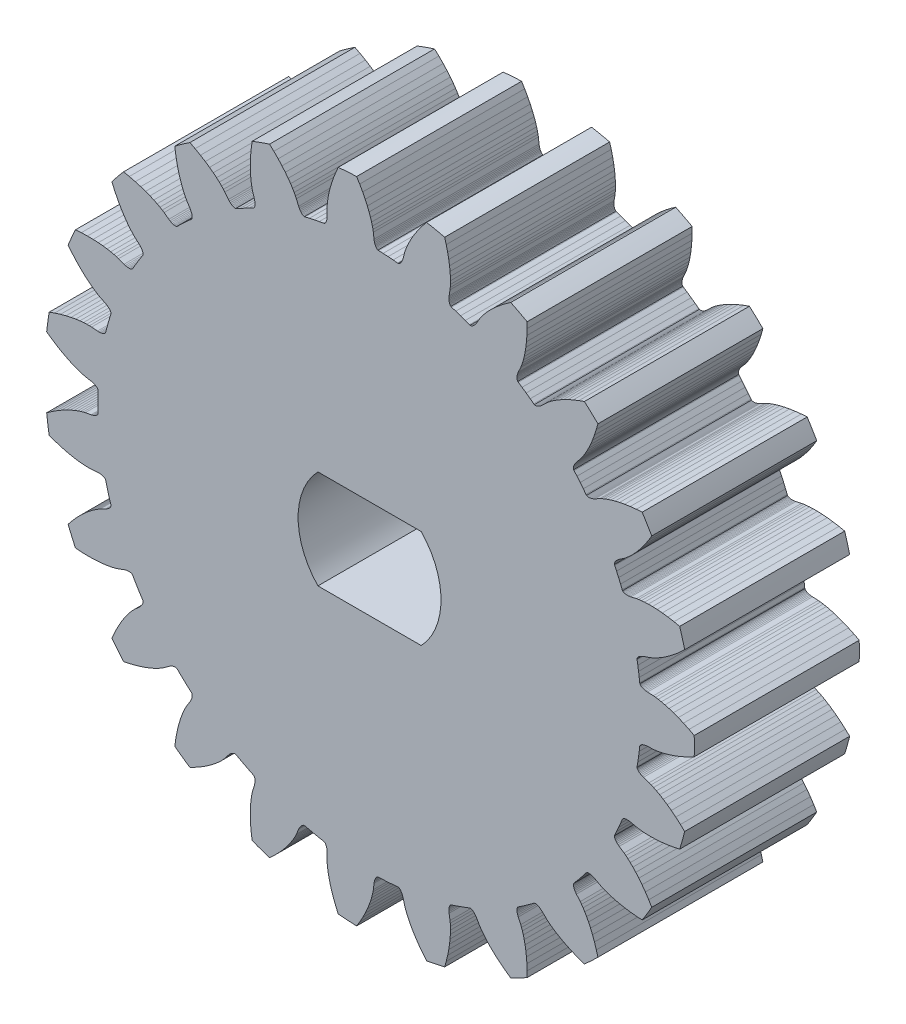
SolidWorks part; units mm, degrees
ref_plane "Front Plane" through (0, 0, 0) normal (0, 0, 1) x (1, 0, 0)
ref_plane "Top Plane" through (0, 0, 0) normal (0, 1, 0) x (1, 0, 0)
ref_plane "Right Plane" through (0, 0, 0) normal (1, 0, 0) x (0, 0, -1)
sketch "Model" plane through (0, 0, 0) normal (0, 0, 1) x (1, 0, 0)
  line L0 (11.9632, 2.8748) -> (11.7845, 2.7201)
  line L1 (11.7845, 2.7201) -> (11.6135, 2.5841)
  line L2 (11.6135, 2.5841) -> (11.4533, 2.4673)
  line L3 (11.4533, 2.4673) -> (11.3032, 2.3672)
  line L4 (11.3032, 2.3672) -> (11.1651, 2.2832)
  line L5 (11.1651, 2.2832) -> (11.0407, 2.2146)
  line L6 (11.0407, 2.2146) -> (10.931, 2.1599)
  line L7 (10.931, 2.1599) -> (10.8362, 2.1174)
  line L8 (10.8362, 2.1174) -> (10.7574, 2.086)
  line L9 (10.7574, 2.086) -> (10.5425, 2.0156)
  line L10 (10.5425, 2.0156) -> (10.4931, 1.9951)
  line L11 (10.4931, 1.9951) -> (10.4491, 1.9736)
  line L12 (10.4491, 1.9736) -> (10.4106, 1.9511)
  line L13 (10.4106, 1.9511) -> (10.3777, 1.9281)
  line L14 (10.3777, 1.9281) -> (10.3503, 1.9046)
  line L15 (10.3503, 1.9046) -> (10.3284, 1.881)
  line L16 (10.3284, 1.881) -> (10.312, 1.8573)
  line L17 (10.312, 1.8573) -> (10.3011, 1.834)
  line L18 (10.3011, 1.834) -> (10.2958, 1.811)
  line L19 (10.2958, 1.811) -> (10.2967, 1.7834)
  line L20 (10.2967, 1.7834) -> (10.3247, 1.6136)
  line L21 (10.3247, 1.6136) -> (10.3527, 1.4229)
  line L22 (10.3527, 1.4229) -> (10.3772, 1.2318)
  line L23 (10.3772, 1.2318) -> (10.396, 1.0608)
  line L24 (10.396, 1.0608) -> (10.4026, 1.0339)
  line L25 (10.4026, 1.0339) -> (10.4139, 1.0133)
  line L26 (10.4139, 1.0133) -> (10.4307, 0.9937)
  line L27 (10.4307, 0.9937) -> (10.4529, 0.9753)
  line L28 (10.4529, 0.9753) -> (10.4803, 0.9585)
  line L29 (10.4803, 0.9585) -> (10.513, 0.9433)
  line L30 (10.513, 0.9433) -> (10.551, 0.93)
  line L31 (10.551, 0.93) -> (10.5941, 0.9188)
  line L32 (10.5941, 0.9188) -> (10.6422, 0.9099)
  line L33 (10.6422, 0.9099) -> (10.6954, 0.9035)
  line L34 (10.6954, 0.9035) -> (10.9213, 0.8937)
  line L35 (10.9213, 0.8937) -> (11.0057, 0.8847)
  line L36 (11.0057, 0.8847) -> (11.1084, 0.8694)
  line L37 (11.1084, 0.8694) -> (11.2288, 0.8463)
  line L38 (11.2288, 0.8463) -> (11.3671, 0.8138)
  line L39 (11.3671, 0.8138) -> (11.5227, 0.7702)
  line L40 (11.5227, 0.7702) -> (11.6942, 0.7143)
  line L41 (11.6942, 0.7143) -> (11.88, 0.645)
  line L42 (11.88, 0.645) -> (12.0814, 0.5602)
  line L43 (12.0814, 0.5602) -> (12.2952, 0.4594)
  line L44 (12.2952, 0.4594) -> (12.4949, 0.3553)
  line L45 (12.4949, -0.3553) -> (12.2952, -0.4594)
  line L46 (12.2952, -0.4594) -> (12.0814, -0.5602)
  line L47 (12.0814, -0.5602) -> (11.88, -0.645)
  line L48 (11.88, -0.645) -> (11.6942, -0.7143)
  line L49 (11.6942, -0.7143) -> (11.5227, -0.7702)
  line L50 (11.5227, -0.7702) -> (11.3671, -0.8138)
  line L51 (11.3671, -0.8138) -> (11.2288, -0.8463)
  line L52 (11.2288, -0.8463) -> (11.1084, -0.8694)
  line L53 (11.1084, -0.8694) -> (11.0057, -0.8847)
  line L54 (11.0057, -0.8847) -> (10.9213, -0.8937)
  line L55 (10.9213, -0.8937) -> (10.6954, -0.9035)
  line L56 (10.6954, -0.9035) -> (10.6422, -0.9099)
  line L57 (10.6422, -0.9099) -> (10.5941, -0.9188)
  line L58 (10.5941, -0.9188) -> (10.551, -0.93)
  line L59 (10.551, -0.93) -> (10.513, -0.9433)
  line L60 (10.513, -0.9433) -> (10.4803, -0.9585)
  line L61 (10.4803, -0.9585) -> (10.4529, -0.9753)
  line L62 (10.4529, -0.9753) -> (10.4307, -0.9937)
  line L63 (10.4307, -0.9937) -> (10.4139, -1.0133)
  line L64 (10.4139, -1.0133) -> (10.4026, -1.0339)
  line L65 (10.4026, -1.0339) -> (10.396, -1.0608)
  line L66 (10.396, -1.0608) -> (10.3772, -1.2318)
  line L67 (10.3772, -1.2318) -> (10.3527, -1.4229)
  line L68 (10.3527, -1.4229) -> (10.3247, -1.6136)
  line L69 (10.3247, -1.6136) -> (10.2967, -1.7834)
  line L70 (10.2967, -1.7834) -> (10.2958, -1.811)
  line L71 (10.2958, -1.811) -> (10.3011, -1.834)
  line L72 (10.3011, -1.834) -> (10.312, -1.8573)
  line L73 (10.312, -1.8573) -> (10.3284, -1.881)
  line L74 (10.3284, -1.881) -> (10.3503, -1.9046)
  line L75 (10.3503, -1.9046) -> (10.3777, -1.9281)
  line L76 (10.3777, -1.9281) -> (10.4106, -1.9511)
  line L77 (10.4106, -1.9511) -> (10.4491, -1.9736)
  line L78 (10.4491, -1.9736) -> (10.4931, -1.9951)
  line L79 (10.4931, -1.9951) -> (10.5425, -2.0156)
  line L80 (10.5425, -2.0156) -> (10.7574, -2.086)
  line L81 (10.7574, -2.086) -> (10.8362, -2.1174)
  line L82 (10.8362, -2.1174) -> (10.931, -2.1599)
  line L83 (10.931, -2.1599) -> (11.0407, -2.2146)
  line L84 (11.0407, -2.2146) -> (11.1651, -2.2832)
  line L85 (11.1651, -2.2832) -> (11.3032, -2.3672)
  line L86 (11.3032, -2.3672) -> (11.4533, -2.4673)
  line L87 (11.4533, -2.4673) -> (11.6135, -2.5841)
  line L88 (11.6135, -2.5841) -> (11.7845, -2.7201)
  line L89 (11.7845, -2.7201) -> (11.9632, -2.8748)
  line L90 (11.9632, -2.8748) -> (12.1275, -3.0289)
  line L91 (11.9357, -3.7132) -> (11.7153, -3.7596)
  line L92 (11.7153, -3.7596) -> (11.4823, -3.7989)
  line L93 (11.4823, -3.7989) -> (11.2655, -3.8263)
  line L94 (11.2655, -3.8263) -> (11.0678, -3.8429)
  line L95 (11.0678, -3.8429) -> (10.8876, -3.8504)
  line L96 (10.8876, -3.8504) -> (10.726, -3.8504)
  line L97 (10.726, -3.8504) -> (10.5841, -3.8444)
  line L98 (10.5841, -3.8444) -> (10.4619, -3.8342)
  line L99 (10.4619, -3.8342) -> (10.3589, -3.8212)
  line L100 (10.3589, -3.8212) -> (10.2752, -3.8071)
  line L101 (10.2752, -3.8071) -> (10.055, -3.7556)
  line L102 (10.055, -3.7556) -> (10.0021, -3.7474)
  line L103 (10.0021, -3.7474) -> (9.9533, -3.7429)
  line L104 (9.9533, -3.7429) -> (9.9088, -3.7421)
  line L105 (9.9088, -3.7421) -> (9.8687, -3.7447)
  line L106 (9.8687, -3.7447) -> (9.8331, -3.7505)
  line L107 (9.8331, -3.7505) -> (9.8021, -3.7593)
  line L108 (9.8021, -3.7593) -> (9.7758, -3.771)
  line L109 (9.7758, -3.771) -> (9.7544, -3.7853)
  line L110 (9.7544, -3.7853) -> (9.7379, -3.8021)
  line L111 (9.7379, -3.8021) -> (9.7243, -3.8263)
  line L112 (9.7243, -3.8263) -> (9.6601, -3.9858)
  line L113 (9.6601, -3.9858) -> (9.5849, -4.1633)
  line L114 (9.5849, -4.1633) -> (9.5065, -4.3394)
  line L115 (9.5065, -4.3394) -> (9.4337, -4.4952)
  line L116 (9.4337, -4.4952) -> (9.4254, -4.5216)
  line L117 (9.4254, -4.5216) -> (9.4243, -4.5452)
  line L118 (9.4243, -4.5452) -> (9.4285, -4.5706)
  line L119 (9.4285, -4.5706) -> (9.4379, -4.5978)
  line L120 (9.4379, -4.5978) -> (9.4526, -4.6265)
  line L121 (9.4526, -4.6265) -> (9.4727, -4.6565)
  line L122 (9.4727, -4.6565) -> (9.4982, -4.6875)
  line L123 (9.4982, -4.6875) -> (9.5292, -4.7195)
  line L124 (9.5292, -4.7195) -> (9.5657, -4.7521)
  line L125 (9.5657, -4.7521) -> (9.6078, -4.7852)
  line L126 (9.6078, -4.7852) -> (9.7957, -4.9109)
  line L127 (9.7957, -4.9109) -> (9.8631, -4.9625)
  line L128 (9.8631, -4.9625) -> (9.943, -5.0289)
  line L129 (9.943, -5.0289) -> (10.0338, -5.1112)
  line L130 (10.0338, -5.1112) -> (10.1351, -5.2109)
  line L131 (10.1351, -5.2109) -> (10.2454, -5.329)
  line L132 (10.2454, -5.329) -> (10.3629, -5.4658)
  line L133 (10.3629, -5.4658) -> (10.4857, -5.6216)
  line L134 (10.4857, -5.6216) -> (10.6137, -5.7987)
  line L135 (10.6137, -5.7987) -> (10.744, -5.9959)
  line L136 (10.744, -5.9959) -> (10.8605, -6.1886)
  line L137 (10.4913, -6.7958) -> (10.2666, -6.7809)
  line L138 (10.2666, -6.7809) -> (10.0315, -6.7559)
  line L139 (10.0315, -6.7559) -> (9.8154, -6.7238)
  line L140 (9.8154, -6.7238) -> (9.6206, -6.6864)
  line L141 (9.6206, -6.6864) -> (9.4451, -6.6451)
  line L142 (9.4451, -6.6451) -> (9.2895, -6.6015)
  line L143 (9.2895, -6.6015) -> (9.1544, -6.5574)
  line L144 (9.1544, -6.5574) -> (9.0395, -6.5146)
  line L145 (9.0395, -6.5146) -> (8.9438, -6.4743)
  line L146 (8.9438, -6.4743) -> (8.867, -6.4381)
  line L147 (8.867, -6.4381) -> (8.6689, -6.3291)
  line L148 (8.6689, -6.3291) -> (8.6202, -6.307)
  line L149 (8.6202, -6.307) -> (8.5744, -6.2895)
  line L150 (8.5744, -6.2895) -> (8.5318, -6.2767)
  line L151 (8.5318, -6.2767) -> (8.4924, -6.2684)
  line L152 (8.4924, -6.2684) -> (8.4566, -6.2643)
  line L153 (8.4566, -6.2643) -> (8.4244, -6.2645)
  line L154 (8.4244, -6.2645) -> (8.3959, -6.2686)
  line L155 (8.3959, -6.2686) -> (8.3714, -6.2767)
  line L156 (8.3714, -6.2767) -> (8.351, -6.2884)
  line L157 (8.351, -6.2884) -> (8.3314, -6.308)
  line L158 (8.3314, -6.308) -> (8.2265, -6.4443)
  line L159 (8.2265, -6.4443) -> (8.1062, -6.5949)
  line L160 (8.1062, -6.5949) -> (7.9832, -6.7433)
  line L161 (7.9832, -6.7433) -> (7.8711, -6.8737)
  line L162 (7.8711, -6.8737) -> (7.8559, -6.8969)
  line L163 (7.8559, -6.8969) -> (7.8486, -6.9193)
  line L164 (7.8486, -6.9193) -> (7.8457, -6.9449)
  line L165 (7.8457, -6.9449) -> (7.8474, -6.9736)
  line L166 (7.8474, -6.9736) -> (7.8538, -7.0052)
  line L167 (7.8538, -7.0052) -> (7.8651, -7.0395)
  line L168 (7.8651, -7.0395) -> (7.8813, -7.0763)
  line L169 (7.8813, -7.0763) -> (7.9025, -7.1154)
  line L170 (7.9025, -7.1154) -> (7.9289, -7.1567)
  line L171 (7.9289, -7.1567) -> (7.9605, -7.1999)
  line L172 (7.9605, -7.1999) -> (8.1075, -7.3717)
  line L173 (8.1075, -7.3717) -> (8.1585, -7.4395)
  line L174 (8.1585, -7.4395) -> (8.2175, -7.525)
  line L175 (8.2175, -7.525) -> (8.2828, -7.6288)
  line L176 (8.2828, -7.6288) -> (8.3534, -7.7521)
  line L177 (8.3534, -7.7521) -> (8.4277, -7.8955)
  line L178 (8.4277, -7.8955) -> (8.5039, -8.059)
  line L179 (8.5039, -8.059) -> (8.5802, -8.2421)
  line L180 (8.5802, -8.2421) -> (8.6556, -8.4472)
  line L181 (8.6556, -8.4472) -> (8.7279, -8.6722)
  line L182 (8.7279, -8.6722) -> (8.7881, -8.8892)
  line L183 (8.2688, -9.3743) -> (8.0564, -9.2993)
  line L184 (8.0564, -9.2993) -> (7.8368, -9.2119)
  line L185 (7.8368, -9.2119) -> (7.6374, -9.1226)
  line L186 (7.6374, -9.1226) -> (7.4599, -9.0341)
  line L187 (7.4599, -9.0341) -> (7.302, -8.9469)
  line L188 (7.302, -8.9469) -> (7.1639, -8.8629)
  line L189 (7.1639, -8.8629) -> (7.0458, -8.7841)
  line L190 (7.0458, -8.7841) -> (6.9467, -8.7118)
  line L191 (6.9467, -8.7118) -> (6.8654, -8.6472)
  line L192 (6.8654, -8.6472) -> (6.8012, -8.5917)
  line L193 (6.8012, -8.5917) -> (6.6398, -8.4333)
  line L194 (6.6398, -8.4333) -> (6.5989, -8.3988)
  line L195 (6.5989, -8.3988) -> (6.5596, -8.3696)
  line L196 (6.5596, -8.3696) -> (6.522, -8.3458)
  line L197 (6.522, -8.3458) -> (6.4863, -8.3271)
  line L198 (6.4863, -8.3271) -> (6.4529, -8.3136)
  line L199 (6.4529, -8.3136) -> (6.4218, -8.305)
  line L200 (6.4218, -8.305) -> (6.3933, -8.3014)
  line L201 (6.3933, -8.3014) -> (6.3675, -8.3025)
  line L202 (6.3675, -8.3025) -> (6.3447, -8.3083)
  line L203 (6.3447, -8.3083) -> (6.3206, -8.3218)
  line L204 (6.3206, -8.3218) -> (6.1828, -8.4248)
  line L205 (6.1828, -8.4248) -> (6.0263, -8.5373)
  line L206 (6.0263, -8.5373) -> (5.8678, -8.6471)
  line L207 (5.8678, -8.6471) -> (5.7247, -8.7424)
  line L208 (5.7247, -8.7424) -> (5.7038, -8.7606)
  line L209 (5.7038, -8.7606) -> (5.6908, -8.7802)
  line L210 (5.6908, -8.7802) -> (5.6811, -8.8041)
  line L211 (5.6811, -8.8041) -> (5.675, -8.8322)
  line L212 (5.675, -8.8322) -> (5.6726, -8.8644)
  line L213 (5.6726, -8.8644) -> (5.6742, -8.9004)
  line L214 (5.6742, -8.9004) -> (5.6798, -8.9402)
  line L215 (5.6798, -8.9402) -> (5.6897, -8.9836)
  line L216 (5.6897, -8.9836) -> (5.704, -9.0305)
  line L217 (5.704, -9.0305) -> (5.7228, -9.0806)
  line L218 (5.7228, -9.0806) -> (5.818, -9.2857)
  line L219 (5.818, -9.2857) -> (5.8488, -9.3648)
  line L220 (5.8488, -9.3648) -> (5.8825, -9.463)
  line L221 (5.8825, -9.463) -> (5.9174, -9.5805)
  line L222 (5.9174, -9.5805) -> (5.9521, -9.7183)
  line L223 (5.9521, -9.7183) -> (5.985, -9.8765)
  line L224 (5.985, -9.8765) -> (6.0143, -10.0545)
  line L225 (6.0143, -10.0545) -> (6.0383, -10.2514)
  line L226 (6.0383, -10.2514) -> (6.0556, -10.4692)
  line L227 (6.0556, -10.4692) -> (6.0645, -10.7054)
  line L228 (6.0645, -10.7054) -> (6.064, -10.9306)
  line L229 (5.433, -11.2575) -> (5.2487, -11.1281)
  line L230 (5.2487, -11.1281) -> (5.0608, -10.9846)
  line L231 (5.0608, -10.9846) -> (4.8929, -10.8449)
  line L232 (4.8929, -10.8449) -> (4.7459, -10.7117)
  line L233 (4.7459, -10.7117) -> (4.6174, -10.5852)
  line L234 (4.6174, -10.5852) -> (4.5071, -10.4671)
  line L235 (4.5071, -10.4671) -> (4.4146, -10.3592)
  line L236 (4.4146, -10.3592) -> (4.3387, -10.263)
  line L237 (4.3387, -10.263) -> (4.2778, -10.1788)
  line L238 (4.2778, -10.1788) -> (4.231, -10.108)
  line L239 (4.231, -10.108) -> (4.1183, -9.9119)
  line L240 (4.1183, -9.9119) -> (4.0882, -9.8677)
  line L241 (4.0882, -9.8677) -> (4.0582, -9.829)
  line L242 (4.0582, -9.829) -> (4.0284, -9.7959)
  line L243 (4.0284, -9.7959) -> (3.9992, -9.7683)
  line L244 (3.9992, -9.7683) -> (3.9706, -9.7463)
  line L245 (3.9706, -9.7463) -> (3.943, -9.7296)
  line L246 (3.943, -9.7296) -> (3.9165, -9.7184)
  line L247 (3.9165, -9.7184) -> (3.8914, -9.7125)
  line L248 (3.8914, -9.7125) -> (3.8679, -9.712)
  line L249 (3.8679, -9.712) -> (3.841, -9.7185)
  line L250 (3.841, -9.7185) -> (3.6805, -9.7804)
  line L251 (3.6805, -9.7804) -> (3.4995, -9.8466)
  line L252 (3.4995, -9.8466) -> (3.3173, -9.9095)
  line L253 (3.3173, -9.9095) -> (3.1538, -9.9628)
  line L254 (3.1538, -9.9628) -> (3.1287, -9.9746)
  line L255 (3.1287, -9.9746) -> (3.1109, -9.99)
  line L256 (3.1109, -9.99) -> (3.0951, -10.0104)
  line L257 (3.0951, -10.0104) -> (3.0816, -10.0358)
  line L258 (3.0816, -10.0358) -> (3.0707, -10.0661)
  line L259 (3.0707, -10.0661) -> (3.0625, -10.1012)
  line L260 (3.0625, -10.1012) -> (3.0572, -10.1411)
  line L261 (3.0572, -10.1411) -> (3.055, -10.1856)
  line L262 (3.055, -10.1856) -> (3.0561, -10.2345)
  line L263 (3.0561, -10.2345) -> (3.0607, -10.2878)
  line L264 (3.0607, -10.2878) -> (3.097, -10.5111)
  line L265 (3.097, -10.5111) -> (3.1053, -10.5955)
  line L266 (3.1053, -10.5955) -> (3.1113, -10.6992)
  line L267 (3.1113, -10.6992) -> (3.1132, -10.8218)
  line L268 (3.1132, -10.8218) -> (3.1094, -10.9638)
  line L269 (3.1094, -10.9638) -> (3.0984, -11.125)
  line L270 (3.0984, -11.125) -> (3.0786, -11.3043)
  line L271 (3.0786, -11.3043) -> (3.0486, -11.5003)
  line L272 (3.0486, -11.5003) -> (3.0065, -11.7147)
  line L273 (3.0065, -11.7147) -> (2.9513, -11.9446)
  line L274 (2.9513, -11.9446) -> (2.8901, -12.1613)
  line L275 (2.1943, -12.3059) -> (2.0517, -12.1315)
  line L276 (2.0517, -12.1315) -> (1.9096, -11.9427)
  line L277 (1.9096, -11.9427) -> (1.7855, -11.7628)
  line L278 (1.7855, -11.7628) -> (1.6799, -11.5949)
  line L279 (1.6799, -11.5949) -> (1.5903, -11.4384)
  line L280 (1.5903, -11.4384) -> (1.516, -11.2949)
  line L281 (1.516, -11.2949) -> (1.456, -11.1661)
  line L282 (1.456, -11.1661) -> (1.4089, -11.0529)
  line L283 (1.4089, -11.0529) -> (1.373, -10.9555)
  line L284 (1.373, -10.9555) -> (1.347, -10.8747)
  line L285 (1.347, -10.8747) -> (1.2914, -10.6555)
  line L286 (1.2914, -10.6555) -> (1.2744, -10.6048)
  line L287 (1.2744, -10.6048) -> (1.2559, -10.5594)
  line L288 (1.2559, -10.5594) -> (1.2361, -10.5195)
  line L289 (1.2361, -10.5195) -> (1.2154, -10.4851)
  line L290 (1.2154, -10.4851) -> (1.1939, -10.4561)
  line L291 (1.1939, -10.4561) -> (1.1718, -10.4327)
  line L292 (1.1718, -10.4327) -> (1.1493, -10.4147)
  line L293 (1.1493, -10.4147) -> (1.1267, -10.4023)
  line L294 (1.1267, -10.4023) -> (1.1042, -10.3954)
  line L295 (1.1042, -10.3954) -> (1.0765, -10.3944)
  line L296 (1.0765, -10.3944) -> (0.9053, -10.4107)
  line L297 (0.9053, -10.4107) -> (0.7131, -10.4256)
  line L298 (0.7131, -10.4256) -> (0.5207, -10.4371)
  line L299 (0.5207, -10.4371) -> (0.3489, -10.4442)
  line L300 (0.3489, -10.4442) -> (0.3216, -10.4489)
  line L301 (0.3216, -10.4489) -> (0.3002, -10.4588)
  line L302 (0.3002, -10.4588) -> (0.2795, -10.4742)
  line L303 (0.2795, -10.4742) -> (0.2597, -10.495)
  line L304 (0.2597, -10.495) -> (0.241, -10.5213)
  line L305 (0.241, -10.5213) -> (0.2236, -10.5529)
  line L306 (0.2236, -10.5529) -> (0.2078, -10.5899)
  line L307 (0.2078, -10.5899) -> (0.1937, -10.6321)
  line L308 (0.1937, -10.6321) -> (0.1815, -10.6795)
  line L309 (0.1815, -10.6795) -> (0.1715, -10.7321)
  line L310 (0.1715, -10.7321) -> (0.1463, -10.9568)
  line L311 (0.1463, -10.9568) -> (0.1316, -11.0404)
  line L312 (0.1316, -11.0404) -> (0.1093, -11.1418)
  line L313 (0.1093, -11.1418) -> (0.078, -11.2604)
  line L314 (0.078, -11.2604) -> (0.0361, -11.3962)
  line L315 (0.0361, -11.3962) -> (-0.018, -11.5484)
  line L316 (-0.018, -11.5484) -> (-0.0854, -11.7157)
  line L317 (-0.0854, -11.7157) -> (-0.1672, -11.8964)
  line L318 (-0.1672, -11.8964) -> (-0.2656, -12.0915)
  line L319 (-0.2656, -12.0915) -> (-0.3807, -12.2979)
  line L320 (-0.3807, -12.2979) -> (-0.4982, -12.4901)
  line L321 (-1.2072, -12.4416) -> (-1.2974, -12.2352)
  line L322 (-1.2974, -12.2352) -> (-1.3834, -12.015)
  line L323 (-1.3834, -12.015) -> (-1.4542, -11.8083)
  line L324 (-1.4542, -11.8083) -> (-1.5107, -11.6182)
  line L325 (-1.5107, -11.6182) -> (-1.5547, -11.4433)
  line L326 (-1.5547, -11.4433) -> (-1.5876, -11.2851)
  line L327 (-1.5876, -11.2851) -> (-1.6106, -11.1449)
  line L328 (-1.6106, -11.1449) -> (-1.6254, -11.0232)
  line L329 (-1.6254, -11.0232) -> (-1.6337, -10.9196)
  line L330 (-1.6337, -10.9196) -> (-1.6369, -10.8349)
  line L331 (-1.6369, -10.8349) -> (-1.6313, -10.6088)
  line L332 (-1.6313, -10.6088) -> (-1.634, -10.5553)
  line L333 (-1.634, -10.5553) -> (-1.6396, -10.5067)
  line L334 (-1.6396, -10.5067) -> (-1.6478, -10.4629)
  line L335 (-1.6478, -10.4629) -> (-1.6585, -10.4242)
  line L336 (-1.6585, -10.4242) -> (-1.6714, -10.3905)
  line L337 (-1.6714, -10.3905) -> (-1.6864, -10.3619)
  line L338 (-1.6864, -10.3619) -> (-1.7032, -10.3386)
  line L339 (-1.7032, -10.3386) -> (-1.7216, -10.3205)
  line L340 (-1.7216, -10.3205) -> (-1.7414, -10.3078)
  line L341 (-1.7414, -10.3078) -> (-1.7678, -10.2994)
  line L342 (-1.7678, -10.2994) -> (-1.9371, -10.2689)
  line L343 (-1.9371, -10.2689) -> (-2.1261, -10.2314)
  line L344 (-2.1261, -10.2314) -> (-2.3145, -10.1905)
  line L345 (-2.3145, -10.1905) -> (-2.4819, -10.151)
  line L346 (-2.4819, -10.151) -> (-2.5094, -10.1482)
  line L347 (-2.5094, -10.1482) -> (-2.5327, -10.152)
  line L348 (-2.5327, -10.152) -> (-2.5567, -10.1612)
  line L349 (-2.5567, -10.1612) -> (-2.5814, -10.1759)
  line L350 (-2.5814, -10.1759) -> (-2.6065, -10.1962)
  line L351 (-2.6065, -10.1962) -> (-2.6318, -10.2219)
  line L352 (-2.6318, -10.2219) -> (-2.657, -10.2532)
  line L353 (-2.657, -10.2532) -> (-2.682, -10.2901)
  line L354 (-2.682, -10.2901) -> (-2.7065, -10.3325)
  line L355 (-2.7065, -10.3325) -> (-2.7303, -10.3804)
  line L356 (-2.7303, -10.3804) -> (-2.8152, -10.59)
  line L357 (-2.8152, -10.59) -> (-2.852, -10.6665)
  line L358 (-2.852, -10.6665) -> (-2.9008, -10.7582)
  line L359 (-2.9008, -10.7582) -> (-2.9629, -10.8639)
  line L360 (-2.9629, -10.8639) -> (-3.0398, -10.9833)
  line L361 (-3.0398, -10.9833) -> (-3.133, -11.1153)
  line L362 (-3.133, -11.1153) -> (-3.2431, -11.2582)
  line L363 (-3.2431, -11.2582) -> (-3.3706, -11.4101)
  line L364 (-3.3706, -11.4101) -> (-3.518, -11.5714)
  line L365 (-3.518, -11.5714) -> (-3.6845, -11.7391)
  line L366 (-3.6845, -11.7391) -> (-3.8495, -11.8925)
  line L367 (-4.5191, -11.6545) -> (-4.5503, -11.4314)
  line L368 (-4.5503, -11.4314) -> (-4.5737, -11.1962)
  line L369 (-4.5737, -11.1962) -> (-4.5862, -10.9781)
  line L370 (-4.5862, -10.9781) -> (-4.5892, -10.7798)
  line L371 (-4.5892, -10.7798) -> (-4.5844, -10.5995)
  line L372 (-4.5844, -10.5995) -> (-4.5734, -10.4383)
  line L373 (-4.5734, -10.4383) -> (-4.5577, -10.2971)
  line L374 (-4.5577, -10.2971) -> (-4.5392, -10.1759)
  line L375 (-4.5392, -10.1759) -> (-4.5192, -10.0739)
  line L376 (-4.5192, -10.0739) -> (-4.4994, -9.9914)
  line L377 (-4.4994, -9.9914) -> (-4.433, -9.7753)
  line L378 (-4.433, -9.7753) -> (-4.4212, -9.7231)
  line L379 (-4.4212, -9.7231) -> (-4.4135, -9.6747)
  line L380 (-4.4135, -9.6747) -> (-4.4096, -9.6304)
  line L381 (-4.4096, -9.6304) -> (-4.4094, -9.5902)
  line L382 (-4.4094, -9.5902) -> (-4.4128, -9.5542)
  line L383 (-4.4128, -9.5542) -> (-4.4195, -9.5227)
  line L384 (-4.4195, -9.5227) -> (-4.4293, -9.4957)
  line L385 (-4.4293, -9.4957) -> (-4.4422, -9.4733)
  line L386 (-4.4422, -9.4733) -> (-4.4578, -9.4557)
  line L387 (-4.4578, -9.4557) -> (-4.481, -9.4405)
  line L388 (-4.481, -9.4405) -> (-4.6357, -9.3655)
  line L389 (-4.6357, -9.3655) -> (-4.8077, -9.2784)
  line L390 (-4.8077, -9.2784) -> (-4.978, -9.1882)
  line L391 (-4.978, -9.1882) -> (-5.1285, -9.105)
  line L392 (-5.1285, -9.105) -> (-5.1543, -9.0948)
  line L393 (-5.1543, -9.0948) -> (-5.1777, -9.0922)
  line L394 (-5.1777, -9.0922) -> (-5.2034, -9.0946)
  line L395 (-5.2034, -9.0946) -> (-5.2311, -9.1021)
  line L396 (-5.2311, -9.1021) -> (-5.2608, -9.1148)
  line L397 (-5.2608, -9.1148) -> (-5.2921, -9.1328)
  line L398 (-5.2921, -9.1328) -> (-5.3248, -9.1561)
  line L399 (-5.3248, -9.1561) -> (-5.3588, -9.1849)
  line L400 (-5.3588, -9.1849) -> (-5.3938, -9.2191)
  line L401 (-5.3938, -9.2191) -> (-5.4297, -9.2588)
  line L402 (-5.4297, -9.2588) -> (-5.568, -9.4378)
  line L403 (-5.568, -9.4378) -> (-5.624, -9.5015)
  line L404 (-5.624, -9.5015) -> (-5.6957, -9.5766)
  line L405 (-5.6957, -9.5766) -> (-5.784, -9.6616)
  line L406 (-5.784, -9.6616) -> (-5.8904, -9.7559)
  line L407 (-5.8904, -9.7559) -> (-6.0157, -9.8579)
  line L408 (-6.0157, -9.8579) -> (-6.1603, -9.9657)
  line L409 (-6.1603, -9.9657) -> (-6.324, -10.0776)
  line L410 (-6.324, -10.0776) -> (-6.5094, -10.1932)
  line L411 (-6.5094, -10.1932) -> (-6.7151, -10.3097)
  line L412 (-6.7151, -10.3097) -> (-6.9153, -10.4129)
  line L413 (-7.4959, -10.0031) -> (-7.4657, -9.7799)
  line L414 (-7.4657, -9.7799) -> (-7.4248, -9.5471)
  line L415 (-7.4248, -9.5471) -> (-7.3779, -9.3337)
  line L416 (-7.3779, -9.3337) -> (-7.3274, -9.1419)
  line L417 (-7.3274, -9.1419) -> (-7.2741, -8.9696)
  line L418 (-7.2741, -8.9696) -> (-7.22, -8.8173)
  line L419 (-7.22, -8.8173) -> (-7.1668, -8.6856)
  line L420 (-7.1668, -8.6856) -> (-7.1163, -8.5739)
  line L421 (-7.1163, -8.5739) -> (-7.0695, -8.4811)
  line L422 (-7.0695, -8.4811) -> (-7.0282, -8.407)
  line L423 (-7.0282, -8.407) -> (-6.906, -8.2168)
  line L424 (-6.906, -8.2168) -> (-6.8805, -8.1697)
  line L425 (-6.8805, -8.1697) -> (-6.86, -8.1252)
  line L426 (-6.86, -8.1252) -> (-6.8443, -8.0836)
  line L427 (-6.8443, -8.0836) -> (-6.8333, -8.0449)
  line L428 (-6.8333, -8.0449) -> (-6.8268, -8.0094)
  line L429 (-6.8268, -8.0094) -> (-6.8248, -7.9772)
  line L430 (-6.8248, -7.9772) -> (-6.827, -7.9485)
  line L431 (-6.827, -7.9485) -> (-6.8333, -7.9235)
  line L432 (-6.8333, -7.9235) -> (-6.8436, -7.9024)
  line L433 (-6.8436, -7.9024) -> (-6.8618, -7.8815)
  line L434 (-6.8618, -7.8815) -> (-6.9906, -7.7675)
  line L435 (-6.9906, -7.7675) -> (-7.1327, -7.6372)
  line L436 (-7.1327, -7.6372) -> (-7.2724, -7.5044)
  line L437 (-7.2724, -7.5044) -> (-7.3949, -7.3837)
  line L438 (-7.3949, -7.3837) -> (-7.4169, -7.3669)
  line L439 (-7.4169, -7.3669) -> (-7.4387, -7.3581)
  line L440 (-7.4387, -7.3581) -> (-7.4641, -7.3535)
  line L441 (-7.4641, -7.3535) -> (-7.4929, -7.3532)
  line L442 (-7.4929, -7.3532) -> (-7.5248, -7.3575)
  line L443 (-7.5248, -7.3575) -> (-7.5598, -7.3664)
  line L444 (-7.5598, -7.3664) -> (-7.5976, -7.38)
  line L445 (-7.5976, -7.38) -> (-7.6381, -7.3985)
  line L446 (-7.6381, -7.3985) -> (-7.6811, -7.422)
  line L447 (-7.6811, -7.422) -> (-7.7263, -7.4506)
  line L448 (-7.7263, -7.4506) -> (-7.9078, -7.5856)
  line L449 (-7.9078, -7.5856) -> (-7.9789, -7.6318)
  line L450 (-7.9789, -7.6318) -> (-8.0683, -7.6848)
  line L451 (-8.0683, -7.6848) -> (-8.1762, -7.7429)
  line L452 (-8.1762, -7.7429) -> (-8.3041, -7.8049)
  line L453 (-8.3041, -7.8049) -> (-8.4523, -7.8693)
  line L454 (-8.4523, -7.8693) -> (-8.6205, -7.9342)
  line L455 (-8.6205, -7.9342) -> (-8.8084, -7.9977)
  line L456 (-8.8084, -7.9977) -> (-9.0182, -8.059)
  line L457 (-9.0182, -8.059) -> (-9.2476, -8.1157)
  line L458 (-9.2476, -8.1157) -> (-9.4682, -8.161)
  line L459 (-9.9167, -7.6098) -> (-9.8275, -7.403)
  line L460 (-9.8275, -7.403) -> (-9.7252, -7.1899)
  line L461 (-9.7252, -7.1899) -> (-9.6225, -6.997)
  line L462 (-9.6225, -6.997) -> (-9.5221, -6.826)
  line L463 (-9.5221, -6.826) -> (-9.4243, -6.6744)
  line L464 (-9.4243, -6.6744) -> (-9.3312, -6.5424)
  line L465 (-9.3312, -6.5424) -> (-9.2444, -6.4299)
  line L466 (-9.2444, -6.4299) -> (-9.1656, -6.336)
  line L467 (-9.1656, -6.336) -> (-9.0955, -6.2593)
  line L468 (-9.0955, -6.2593) -> (-9.0358, -6.1991)
  line L469 (-9.0358, -6.1991) -> (-8.8667, -6.0488)
  line L470 (-8.8667, -6.0488) -> (-8.8295, -6.0104)
  line L471 (-8.8295, -6.0104) -> (-8.7978, -5.9731)
  line L472 (-8.7978, -5.9731) -> (-8.7714, -5.9372)
  line L473 (-8.7714, -5.9372) -> (-8.7504, -5.903)
  line L474 (-8.7504, -5.903) -> (-8.7346, -5.8705)
  line L475 (-8.7346, -5.8705) -> (-8.7239, -5.8401)
  line L476 (-8.7239, -5.8401) -> (-8.7183, -5.8119)
  line L477 (-8.7183, -5.8119) -> (-8.7177, -5.7861)
  line L478 (-8.7177, -5.7861) -> (-8.7219, -5.7629)
  line L479 (-8.7219, -5.7629) -> (-8.7338, -5.7379)
  line L480 (-8.7338, -5.7379) -> (-8.8271, -5.5934)
  line L481 (-8.8271, -5.5934) -> (-8.9287, -5.4297)
  line L482 (-8.9287, -5.4297) -> (-9.0273, -5.2641)
  line L483 (-9.0273, -5.2641) -> (-9.1127, -5.1148)
  line L484 (-9.1127, -5.1148) -> (-9.1295, -5.0927)
  line L485 (-9.1295, -5.0927) -> (-9.1481, -5.0783)
  line L486 (-9.1481, -5.0783) -> (-9.1713, -5.067)
  line L487 (-9.1713, -5.067) -> (-9.1989, -5.059)
  line L488 (-9.1989, -5.059) -> (-9.2308, -5.0545)
  line L489 (-9.2308, -5.0545) -> (-9.2669, -5.0536)
  line L490 (-9.2669, -5.0536) -> (-9.307, -5.0565)
  line L491 (-9.307, -5.0565) -> (-9.351, -5.0634)
  line L492 (-9.351, -5.0634) -> (-9.3987, -5.0744)
  line L493 (-9.3987, -5.0744) -> (-9.45, -5.0898)
  line L494 (-9.45, -5.0898) -> (-9.6611, -5.1708)
  line L495 (-9.6611, -5.1708) -> (-9.7421, -5.1961)
  line L496 (-9.7421, -5.1961) -> (-9.8424, -5.223)
  line L497 (-9.8424, -5.223) -> (-9.962, -5.2498)
  line L498 (-9.962, -5.2498) -> (-10.1018, -5.2751)
  line L499 (-10.1018, -5.2751) -> (-10.2619, -5.2971)
  line L500 (-10.2619, -5.2971) -> (-10.4415, -5.3141)
  line L501 (-10.4415, -5.3141) -> (-10.6395, -5.3246)
  line L502 (-10.6395, -5.3246) -> (-10.858, -5.3271)
  line L503 (-10.858, -5.3271) -> (-11.0943, -5.3198)
  line L504 (-11.0943, -5.3198) -> (-11.3189, -5.3039)
  line L505 (-11.6021, -4.6521) -> (-11.4603, -4.4771)
  line L506 (-11.4603, -4.4771) -> (-11.3044, -4.2994)
  line L507 (-11.3044, -4.2994) -> (-11.1535, -4.1414)
  line L508 (-11.1535, -4.1414) -> (-11.0106, -4.0038)
  line L509 (-11.0106, -4.0038) -> (-10.8756, -3.8843)
  line L510 (-10.8756, -3.8843) -> (-10.7502, -3.7823)
  line L511 (-10.7502, -3.7823) -> (-10.6364, -3.6973)
  line L512 (-10.6364, -3.6973) -> (-10.5351, -3.6282)
  line L513 (-10.5351, -3.6282) -> (-10.447, -3.5732)
  line L514 (-10.447, -3.5732) -> (-10.3732, -3.5314)
  line L515 (-10.3732, -3.5314) -> (-10.1699, -3.4323)
  line L516 (-10.1699, -3.4323) -> (-10.1237, -3.4053)
  line L517 (-10.1237, -3.4053) -> (-10.083, -3.378)
  line L518 (-10.083, -3.378) -> (-10.048, -3.3506)
  line L519 (-10.048, -3.3506) -> (-10.0185, -3.3232)
  line L520 (-10.0185, -3.3232) -> (-9.9945, -3.2963)
  line L521 (-9.9945, -3.2963) -> (-9.976, -3.2698)
  line L522 (-9.976, -3.2698) -> (-9.963, -3.2442)
  line L523 (-9.963, -3.2442) -> (-9.9555, -3.2195)
  line L524 (-9.9555, -3.2195) -> (-9.9533, -3.1961)
  line L525 (-9.9533, -3.1961) -> (-9.958, -3.1688)
  line L526 (-9.958, -3.1688) -> (-10.0088, -3.0045)
  line L527 (-10.0088, -3.0045) -> (-10.0625, -2.8194)
  line L528 (-10.0625, -2.8194) -> (-10.1128, -2.6333)
  line L529 (-10.1128, -2.6333) -> (-10.1548, -2.4665)
  line L530 (-10.1548, -2.4665) -> (-10.1649, -2.4407)
  line L531 (-10.1649, -2.4407) -> (-10.179, -2.4219)
  line L532 (-10.179, -2.4219) -> (-10.1982, -2.4047)
  line L533 (-10.1982, -2.4047) -> (-10.2227, -2.3896)
  line L534 (-10.2227, -2.3896) -> (-10.2522, -2.3766)
  line L535 (-10.2522, -2.3766) -> (-10.2867, -2.366)
  line L536 (-10.2867, -2.366) -> (-10.3261, -2.358)
  line L537 (-10.3261, -2.358) -> (-10.3703, -2.3528)
  line L538 (-10.3703, -2.3528) -> (-10.4192, -2.3505)
  line L539 (-10.4192, -2.3505) -> (-10.4727, -2.3515)
  line L540 (-10.4727, -2.3515) -> (-10.6979, -2.3725)
  line L541 (-10.6979, -2.3725) -> (-10.7827, -2.375)
  line L542 (-10.7827, -2.375) -> (-10.8866, -2.3739)
  line L543 (-10.8866, -2.3739) -> (-11.009, -2.3674)
  line L544 (-11.009, -2.3674) -> (-11.1504, -2.354)
  line L545 (-11.1504, -2.354) -> (-11.3105, -2.332)
  line L546 (-11.3105, -2.332) -> (-11.488, -2.3)
  line L547 (-11.488, -2.3) -> (-11.6816, -2.2567)
  line L548 (-11.6816, -2.2567) -> (-11.8926, -2.2001)
  line L549 (-11.8926, -2.2001) -> (-12.1181, -2.1293)
  line L550 (-12.1181, -2.1293) -> (-12.3302, -2.0534)
  line L551 (-12.4269, -1.3494) -> (-12.2432, -1.2191)
  line L552 (-12.2432, -1.2191) -> (-12.0452, -1.0901)
  line L553 (-12.0452, -1.0901) -> (-11.8572, -0.9787)
  line L554 (-11.8572, -0.9787) -> (-11.6826, -0.8847)
  line L555 (-11.6826, -0.8847) -> (-11.5203, -0.806)
  line L556 (-11.5203, -0.806) -> (-11.372, -0.7417)
  line L557 (-11.372, -0.7417) -> (-11.2395, -0.6906)
  line L558 (-11.2395, -0.6906) -> (-11.1233, -0.6513)
  line L559 (-11.1233, -0.6513) -> (-11.0236, -0.6222)
  line L560 (-11.0236, -0.6222) -> (-10.9413, -0.6018)
  line L561 (-10.9413, -0.6018) -> (-10.7188, -0.5612)
  line L562 (-10.7188, -0.5612) -> (-10.667, -0.5477)
  line L563 (-10.667, -0.5477) -> (-10.6205, -0.5323)
  line L564 (-10.6205, -0.5323) -> (-10.5793, -0.5154)
  line L565 (-10.5793, -0.5154) -> (-10.5436, -0.497)
  line L566 (-10.5436, -0.497) -> (-10.5132, -0.4775)
  line L567 (-10.5132, -0.4775) -> (-10.4883, -0.4571)
  line L568 (-10.4883, -0.4571) -> (-10.4689, -0.4359)
  line L569 (-10.4689, -0.4359) -> (-10.4549, -0.4142)
  line L570 (-10.4549, -0.4142) -> (-10.4465, -0.3922)
  line L571 (-10.4465, -0.3922) -> (-10.4436, -0.3647)
  line L572 (-10.4436, -0.3647) -> (-10.4483, -0.1927)
  line L573 (-10.4483, -0.1927) -> (-10.45, 0)
  line L574 (-10.45, 0) -> (-10.4483, 0.1927)
  line L575 (-10.4483, 0.1927) -> (-10.4436, 0.3647)
  line L576 (-10.4436, 0.3647) -> (-10.4465, 0.3922)
  line L577 (-10.4465, 0.3922) -> (-10.4549, 0.4142)
  line L578 (-10.4549, 0.4142) -> (-10.4689, 0.4359)
  line L579 (-10.4689, 0.4359) -> (-10.4883, 0.4571)
  line L580 (-10.4883, 0.4571) -> (-10.5132, 0.4775)
  line L581 (-10.5132, 0.4775) -> (-10.5436, 0.497)
  line L582 (-10.5436, 0.497) -> (-10.5793, 0.5154)
  line L583 (-10.5793, 0.5154) -> (-10.6205, 0.5323)
  line L584 (-10.6205, 0.5323) -> (-10.667, 0.5477)
  line L585 (-10.667, 0.5477) -> (-10.7188, 0.5612)
  line L586 (-10.7188, 0.5612) -> (-10.9413, 0.6018)
  line L587 (-10.9413, 0.6018) -> (-11.0236, 0.6222)
  line L588 (-11.0236, 0.6222) -> (-11.1233, 0.6513)
  line L589 (-11.1233, 0.6513) -> (-11.2395, 0.6906)
  line L590 (-11.2395, 0.6906) -> (-11.372, 0.7417)
  line L591 (-11.372, 0.7417) -> (-11.5203, 0.806)
  line L592 (-11.5203, 0.806) -> (-11.6826, 0.8847)
  line L593 (-11.6826, 0.8847) -> (-11.8572, 0.9787)
  line L594 (-11.8572, 0.9787) -> (-12.0452, 1.0901)
  line L595 (-12.0452, 1.0901) -> (-12.2432, 1.2191)
  line L596 (-12.2432, 1.2191) -> (-12.4269, 1.3494)
  line L597 (-12.3302, 2.0534) -> (-12.1181, 2.1293)
  line L598 (-12.1181, 2.1293) -> (-11.8926, 2.2001)
  line L599 (-11.8926, 2.2001) -> (-11.6816, 2.2567)
  line L600 (-11.6816, 2.2567) -> (-11.488, 2.3)
  line L601 (-11.488, 2.3) -> (-11.3105, 2.332)
  line L602 (-11.3105, 2.332) -> (-11.1504, 2.354)
  line L603 (-11.1504, 2.354) -> (-11.009, 2.3674)
  line L604 (-11.009, 2.3674) -> (-10.8866, 2.3739)
  line L605 (-10.8866, 2.3739) -> (-10.7827, 2.375)
  line L606 (-10.7827, 2.375) -> (-10.6979, 2.3725)
  line L607 (-10.6979, 2.3725) -> (-10.4727, 2.3515)
  line L608 (-10.4727, 2.3515) -> (-10.4192, 2.3505)
  line L609 (-10.4192, 2.3505) -> (-10.3703, 2.3528)
  line L610 (-10.3703, 2.3528) -> (-10.3261, 2.358)
  line L611 (-10.3261, 2.358) -> (-10.2867, 2.366)
  line L612 (-10.2867, 2.366) -> (-10.2522, 2.3766)
  line L613 (-10.2522, 2.3766) -> (-10.2227, 2.3896)
  line L614 (-10.2227, 2.3896) -> (-10.1982, 2.4047)
  line L615 (-10.1982, 2.4047) -> (-10.179, 2.4219)
  line L616 (-10.179, 2.4219) -> (-10.1649, 2.4407)
  line L617 (-10.1649, 2.4407) -> (-10.1548, 2.4665)
  line L618 (-10.1548, 2.4665) -> (-10.1128, 2.6333)
  line L619 (-10.1128, 2.6333) -> (-10.0625, 2.8194)
  line L620 (-10.0625, 2.8194) -> (-10.0088, 3.0045)
  line L621 (-10.0088, 3.0045) -> (-9.958, 3.1688)
  line L622 (-9.958, 3.1688) -> (-9.9533, 3.1961)
  line L623 (-9.9533, 3.1961) -> (-9.9555, 3.2195)
  line L624 (-9.9555, 3.2195) -> (-9.963, 3.2442)
  line L625 (-9.963, 3.2442) -> (-9.976, 3.2698)
  line L626 (-9.976, 3.2698) -> (-9.9945, 3.2963)
  line L627 (-9.9945, 3.2963) -> (-10.0185, 3.3232)
  line L628 (-10.0185, 3.3232) -> (-10.048, 3.3506)
  line L629 (-10.048, 3.3506) -> (-10.083, 3.378)
  line L630 (-10.083, 3.378) -> (-10.1237, 3.4053)
  line L631 (-10.1237, 3.4053) -> (-10.1699, 3.4323)
  line L632 (-10.1699, 3.4323) -> (-10.3732, 3.5314)
  line L633 (-10.3732, 3.5314) -> (-10.447, 3.5732)
  line L634 (-10.447, 3.5732) -> (-10.5351, 3.6282)
  line L635 (-10.5351, 3.6282) -> (-10.6364, 3.6973)
  line L636 (-10.6364, 3.6973) -> (-10.7502, 3.7823)
  line L637 (-10.7502, 3.7823) -> (-10.8756, 3.8843)
  line L638 (-10.8756, 3.8843) -> (-11.0106, 4.0038)
  line L639 (-11.0106, 4.0038) -> (-11.1535, 4.1414)
  line L640 (-11.1535, 4.1414) -> (-11.3044, 4.2994)
  line L641 (-11.3044, 4.2994) -> (-11.4603, 4.4771)
  line L642 (-11.4603, 4.4771) -> (-11.6021, 4.6521)
  line L643 (-11.3189, 5.3039) -> (-11.0943, 5.3198)
  line L644 (-11.0943, 5.3198) -> (-10.858, 5.3271)
  line L645 (-10.858, 5.3271) -> (-10.6395, 5.3246)
  line L646 (-10.6395, 5.3246) -> (-10.4415, 5.3141)
  line L647 (-10.4415, 5.3141) -> (-10.2619, 5.2971)
  line L648 (-10.2619, 5.2971) -> (-10.1018, 5.2751)
  line L649 (-10.1018, 5.2751) -> (-9.962, 5.2498)
  line L650 (-9.962, 5.2498) -> (-9.8424, 5.223)
  line L651 (-9.8424, 5.223) -> (-9.7421, 5.1961)
  line L652 (-9.7421, 5.1961) -> (-9.6611, 5.1708)
  line L653 (-9.6611, 5.1708) -> (-9.45, 5.0898)
  line L654 (-9.45, 5.0898) -> (-9.3987, 5.0744)
  line L655 (-9.3987, 5.0744) -> (-9.351, 5.0634)
  line L656 (-9.351, 5.0634) -> (-9.307, 5.0565)
  line L657 (-9.307, 5.0565) -> (-9.2669, 5.0536)
  line L658 (-9.2669, 5.0536) -> (-9.2308, 5.0545)
  line L659 (-9.2308, 5.0545) -> (-9.1989, 5.059)
  line L660 (-9.1989, 5.059) -> (-9.1713, 5.067)
  line L661 (-9.1713, 5.067) -> (-9.1481, 5.0783)
  line L662 (-9.1481, 5.0783) -> (-9.1295, 5.0927)
  line L663 (-9.1295, 5.0927) -> (-9.1127, 5.1148)
  line L664 (-9.1127, 5.1148) -> (-9.0273, 5.2641)
  line L665 (-9.0273, 5.2641) -> (-8.9287, 5.4297)
  line L666 (-8.9287, 5.4297) -> (-8.8271, 5.5934)
  line L667 (-8.8271, 5.5934) -> (-8.7338, 5.7379)
  line L668 (-8.7338, 5.7379) -> (-8.7219, 5.7629)
  line L669 (-8.7219, 5.7629) -> (-8.7177, 5.7861)
  line L670 (-8.7177, 5.7861) -> (-8.7183, 5.8119)
  line L671 (-8.7183, 5.8119) -> (-8.7239, 5.8401)
  line L672 (-8.7239, 5.8401) -> (-8.7346, 5.8705)
  line L673 (-8.7346, 5.8705) -> (-8.7504, 5.903)
  line L674 (-8.7504, 5.903) -> (-8.7714, 5.9372)
  line L675 (-8.7714, 5.9372) -> (-8.7978, 5.9731)
  line L676 (-8.7978, 5.9731) -> (-8.8295, 6.0104)
  line L677 (-8.8295, 6.0104) -> (-8.8667, 6.0488)
  line L678 (-8.8667, 6.0488) -> (-9.0358, 6.1991)
  line L679 (-9.0358, 6.1991) -> (-9.0955, 6.2593)
  line L680 (-9.0955, 6.2593) -> (-9.1656, 6.336)
  line L681 (-9.1656, 6.336) -> (-9.2444, 6.4299)
  line L682 (-9.2444, 6.4299) -> (-9.3312, 6.5424)
  line L683 (-9.3312, 6.5424) -> (-9.4243, 6.6744)
  line L684 (-9.4243, 6.6744) -> (-9.5221, 6.826)
  line L685 (-9.5221, 6.826) -> (-9.6225, 6.997)
  line L686 (-9.6225, 6.997) -> (-9.7252, 7.1899)
  line L687 (-9.7252, 7.1899) -> (-9.8275, 7.403)
  line L688 (-9.8275, 7.403) -> (-9.9167, 7.6098)
  line L689 (-9.4682, 8.161) -> (-9.2476, 8.1157)
  line L690 (-9.2476, 8.1157) -> (-9.0182, 8.059)
  line L691 (-9.0182, 8.059) -> (-8.8084, 7.9977)
  line L692 (-8.8084, 7.9977) -> (-8.6205, 7.9342)
  line L693 (-8.6205, 7.9342) -> (-8.4523, 7.8693)
  line L694 (-8.4523, 7.8693) -> (-8.3041, 7.8049)
  line L695 (-8.3041, 7.8049) -> (-8.1762, 7.7429)
  line L696 (-8.1762, 7.7429) -> (-8.0683, 7.6848)
  line L697 (-8.0683, 7.6848) -> (-7.9789, 7.6318)
  line L698 (-7.9789, 7.6318) -> (-7.9078, 7.5856)
  line L699 (-7.9078, 7.5856) -> (-7.7263, 7.4506)
  line L700 (-7.7263, 7.4506) -> (-7.6811, 7.422)
  line L701 (-7.6811, 7.422) -> (-7.6381, 7.3985)
  line L702 (-7.6381, 7.3985) -> (-7.5976, 7.38)
  line L703 (-7.5976, 7.38) -> (-7.5598, 7.3664)
  line L704 (-7.5598, 7.3664) -> (-7.5248, 7.3575)
  line L705 (-7.5248, 7.3575) -> (-7.4929, 7.3532)
  line L706 (-7.4929, 7.3532) -> (-7.4641, 7.3535)
  line L707 (-7.4641, 7.3535) -> (-7.4387, 7.3581)
  line L708 (-7.4387, 7.3581) -> (-7.4169, 7.3669)
  line L709 (-7.4169, 7.3669) -> (-7.3949, 7.3837)
  line L710 (-7.3949, 7.3837) -> (-7.2724, 7.5044)
  line L711 (-7.2724, 7.5044) -> (-7.1327, 7.6372)
  line L712 (-7.1327, 7.6372) -> (-6.9906, 7.7675)
  line L713 (-6.9906, 7.7675) -> (-6.8618, 7.8815)
  line L714 (-6.8618, 7.8815) -> (-6.8436, 7.9024)
  line L715 (-6.8436, 7.9024) -> (-6.8333, 7.9235)
  line L716 (-6.8333, 7.9235) -> (-6.827, 7.9485)
  line L717 (-6.827, 7.9485) -> (-6.8248, 7.9772)
  line L718 (-6.8248, 7.9772) -> (-6.8268, 8.0094)
  line L719 (-6.8268, 8.0094) -> (-6.8333, 8.0449)
  line L720 (-6.8333, 8.0449) -> (-6.8443, 8.0836)
  line L721 (-6.8443, 8.0836) -> (-6.86, 8.1252)
  line L722 (-6.86, 8.1252) -> (-6.8805, 8.1697)
  line L723 (-6.8805, 8.1697) -> (-6.906, 8.2168)
  line L724 (-6.906, 8.2168) -> (-7.0282, 8.407)
  line L725 (-7.0282, 8.407) -> (-7.0695, 8.4811)
  line L726 (-7.0695, 8.4811) -> (-7.1163, 8.5739)
  line L727 (-7.1163, 8.5739) -> (-7.1668, 8.6856)
  line L728 (-7.1668, 8.6856) -> (-7.22, 8.8173)
  line L729 (-7.22, 8.8173) -> (-7.2741, 8.9696)
  line L730 (-7.2741, 8.9696) -> (-7.3274, 9.1419)
  line L731 (-7.3274, 9.1419) -> (-7.3779, 9.3337)
  line L732 (-7.3779, 9.3337) -> (-7.4248, 9.5471)
  line L733 (-7.4248, 9.5471) -> (-7.4657, 9.7799)
  line L734 (-7.4657, 9.7799) -> (-7.4959, 10.0031)
  line L735 (-6.9153, 10.4129) -> (-6.7151, 10.3097)
  line L736 (-6.7151, 10.3097) -> (-6.5094, 10.1932)
  line L737 (-6.5094, 10.1932) -> (-6.324, 10.0776)
  line L738 (-6.324, 10.0776) -> (-6.1603, 9.9657)
  line L739 (-6.1603, 9.9657) -> (-6.0157, 9.8579)
  line L740 (-6.0157, 9.8579) -> (-5.8904, 9.7559)
  line L741 (-5.8904, 9.7559) -> (-5.784, 9.6616)
  line L742 (-5.784, 9.6616) -> (-5.6957, 9.5766)
  line L743 (-5.6957, 9.5766) -> (-5.624, 9.5015)
  line L744 (-5.624, 9.5015) -> (-5.568, 9.4378)
  line L745 (-5.568, 9.4378) -> (-5.4297, 9.2588)
  line L746 (-5.4297, 9.2588) -> (-5.3938, 9.2191)
  line L747 (-5.3938, 9.2191) -> (-5.3588, 9.1849)
  line L748 (-5.3588, 9.1849) -> (-5.3248, 9.1561)
  line L749 (-5.3248, 9.1561) -> (-5.2921, 9.1328)
  line L750 (-5.2921, 9.1328) -> (-5.2608, 9.1148)
  line L751 (-5.2608, 9.1148) -> (-5.2311, 9.1021)
  line L752 (-5.2311, 9.1021) -> (-5.2034, 9.0946)
  line L753 (-5.2034, 9.0946) -> (-5.1777, 9.0922)
  line L754 (-5.1777, 9.0922) -> (-5.1543, 9.0948)
  line L755 (-5.1543, 9.0948) -> (-5.1285, 9.105)
  line L756 (-5.1285, 9.105) -> (-4.978, 9.1882)
  line L757 (-4.978, 9.1882) -> (-4.8077, 9.2784)
  line L758 (-4.8077, 9.2784) -> (-4.6357, 9.3655)
  line L759 (-4.6357, 9.3655) -> (-4.481, 9.4405)
  line L760 (-4.481, 9.4405) -> (-4.4578, 9.4557)
  line L761 (-4.4578, 9.4557) -> (-4.4422, 9.4733)
  line L762 (-4.4422, 9.4733) -> (-4.4293, 9.4957)
  line L763 (-4.4293, 9.4957) -> (-4.4195, 9.5227)
  line L764 (-4.4195, 9.5227) -> (-4.4128, 9.5542)
  line L765 (-4.4128, 9.5542) -> (-4.4094, 9.5902)
  line L766 (-4.4094, 9.5902) -> (-4.4096, 9.6304)
  line L767 (-4.4096, 9.6304) -> (-4.4135, 9.6747)
  line L768 (-4.4135, 9.6747) -> (-4.4212, 9.7231)
  line L769 (-4.4212, 9.7231) -> (-4.433, 9.7753)
  line L770 (-4.433, 9.7753) -> (-4.4994, 9.9914)
  line L771 (-4.4994, 9.9914) -> (-4.5192, 10.0739)
  line L772 (-4.5192, 10.0739) -> (-4.5392, 10.1759)
  line L773 (-4.5392, 10.1759) -> (-4.5577, 10.2971)
  line L774 (-4.5577, 10.2971) -> (-4.5734, 10.4383)
  line L775 (-4.5734, 10.4383) -> (-4.5844, 10.5995)
  line L776 (-4.5844, 10.5995) -> (-4.5892, 10.7798)
  line L777 (-4.5892, 10.7798) -> (-4.5862, 10.9781)
  line L778 (-4.5862, 10.9781) -> (-4.5737, 11.1962)
  line L779 (-4.5737, 11.1962) -> (-4.5503, 11.4314)
  line L780 (-4.5503, 11.4314) -> (-4.5191, 11.6545)
  line L781 (-3.8495, 11.8925) -> (-3.6845, 11.7391)
  line L782 (-3.6845, 11.7391) -> (-3.518, 11.5714)
  line L783 (-3.518, 11.5714) -> (-3.3706, 11.4101)
  line L784 (-3.3706, 11.4101) -> (-3.2431, 11.2582)
  line L785 (-3.2431, 11.2582) -> (-3.133, 11.1153)
  line L786 (-3.133, 11.1153) -> (-3.0398, 10.9833)
  line L787 (-3.0398, 10.9833) -> (-2.9629, 10.8639)
  line L788 (-2.9629, 10.8639) -> (-2.9008, 10.7582)
  line L789 (-2.9008, 10.7582) -> (-2.852, 10.6665)
  line L790 (-2.852, 10.6665) -> (-2.8152, 10.59)
  line L791 (-2.8152, 10.59) -> (-2.7303, 10.3804)
  line L792 (-2.7303, 10.3804) -> (-2.7065, 10.3325)
  line L793 (-2.7065, 10.3325) -> (-2.682, 10.2901)
  line L794 (-2.682, 10.2901) -> (-2.657, 10.2532)
  line L795 (-2.657, 10.2532) -> (-2.6318, 10.2219)
  line L796 (-2.6318, 10.2219) -> (-2.6065, 10.1962)
  line L797 (-2.6065, 10.1962) -> (-2.5814, 10.1759)
  line L798 (-2.5814, 10.1759) -> (-2.5567, 10.1612)
  line L799 (-2.5567, 10.1612) -> (-2.5327, 10.152)
  line L800 (-2.5327, 10.152) -> (-2.5094, 10.1482)
  line L801 (-2.5094, 10.1482) -> (-2.4819, 10.151)
  line L802 (-2.4819, 10.151) -> (-2.3145, 10.1905)
  line L803 (-2.3145, 10.1905) -> (-2.1261, 10.2314)
  line L804 (-2.1261, 10.2314) -> (-1.9371, 10.2689)
  line L805 (-1.9371, 10.2689) -> (-1.7678, 10.2994)
  line L806 (-1.7678, 10.2994) -> (-1.7414, 10.3078)
  line L807 (-1.7414, 10.3078) -> (-1.7216, 10.3205)
  line L808 (-1.7216, 10.3205) -> (-1.7032, 10.3386)
  line L809 (-1.7032, 10.3386) -> (-1.6864, 10.3619)
  line L810 (-1.6864, 10.3619) -> (-1.6714, 10.3905)
  line L811 (-1.6714, 10.3905) -> (-1.6585, 10.4242)
  line L812 (-1.6585, 10.4242) -> (-1.6478, 10.4629)
  line L813 (-1.6478, 10.4629) -> (-1.6396, 10.5067)
  line L814 (-1.6396, 10.5067) -> (-1.634, 10.5553)
  line L815 (-1.634, 10.5553) -> (-1.6313, 10.6088)
  line L816 (-1.6313, 10.6088) -> (-1.6369, 10.8349)
  line L817 (-1.6369, 10.8349) -> (-1.6337, 10.9196)
  line L818 (-1.6337, 10.9196) -> (-1.6254, 11.0232)
  line L819 (-1.6254, 11.0232) -> (-1.6106, 11.1449)
  line L820 (-1.6106, 11.1449) -> (-1.5876, 11.2851)
  line L821 (-1.5876, 11.2851) -> (-1.5547, 11.4433)
  line L822 (-1.5547, 11.4433) -> (-1.5107, 11.6182)
  line L823 (-1.5107, 11.6182) -> (-1.4542, 11.8083)
  line L824 (-1.4542, 11.8083) -> (-1.3834, 12.015)
  line L825 (-1.3834, 12.015) -> (-1.2974, 12.2352)
  line L826 (-1.2974, 12.2352) -> (-1.2072, 12.4416)
  line L827 (-0.4982, 12.4901) -> (-0.3807, 12.2979)
  line L828 (-0.3807, 12.2979) -> (-0.2656, 12.0915)
  line L829 (-0.2656, 12.0915) -> (-0.1672, 11.8964)
  line L830 (-0.1672, 11.8964) -> (-0.0854, 11.7157)
  line L831 (-0.0854, 11.7157) -> (-0.018, 11.5484)
  line L832 (-0.018, 11.5484) -> (0.0361, 11.3962)
  line L833 (0.0361, 11.3962) -> (0.078, 11.2604)
  line L834 (0.078, 11.2604) -> (0.1093, 11.1418)
  line L835 (0.1093, 11.1418) -> (0.1316, 11.0404)
  line L836 (0.1316, 11.0404) -> (0.1463, 10.9568)
  line L837 (0.1463, 10.9568) -> (0.1715, 10.7321)
  line L838 (0.1715, 10.7321) -> (0.1815, 10.6795)
  line L839 (0.1815, 10.6795) -> (0.1937, 10.6321)
  line L840 (0.1937, 10.6321) -> (0.2078, 10.5899)
  line L841 (0.2078, 10.5899) -> (0.2236, 10.5529)
  line L842 (0.2236, 10.5529) -> (0.241, 10.5213)
  line L843 (0.241, 10.5213) -> (0.2597, 10.495)
  line L844 (0.2597, 10.495) -> (0.2795, 10.4742)
  line L845 (0.2795, 10.4742) -> (0.3002, 10.4588)
  line L846 (0.3002, 10.4588) -> (0.3216, 10.4489)
  line L847 (0.3216, 10.4489) -> (0.3489, 10.4442)
  line L848 (0.3489, 10.4442) -> (0.5207, 10.4371)
  line L849 (0.5207, 10.4371) -> (0.7131, 10.4256)
  line L850 (0.7131, 10.4256) -> (0.9053, 10.4107)
  line L851 (0.9053, 10.4107) -> (1.0765, 10.3944)
  line L852 (1.0765, 10.3944) -> (1.1042, 10.3954)
  line L853 (1.1042, 10.3954) -> (1.1267, 10.4023)
  line L854 (1.1267, 10.4023) -> (1.1493, 10.4147)
  line L855 (1.1493, 10.4147) -> (1.1718, 10.4327)
  line L856 (1.1718, 10.4327) -> (1.1939, 10.4561)
  line L857 (1.1939, 10.4561) -> (1.2154, 10.4851)
  line L858 (1.2154, 10.4851) -> (1.2361, 10.5195)
  line L859 (1.2361, 10.5195) -> (1.2559, 10.5594)
  line L860 (1.2559, 10.5594) -> (1.2744, 10.6048)
  line L861 (1.2744, 10.6048) -> (1.2914, 10.6555)
  line L862 (1.2914, 10.6555) -> (1.347, 10.8747)
  line L863 (1.347, 10.8747) -> (1.373, 10.9555)
  line L864 (1.373, 10.9555) -> (1.4089, 11.0529)
  line L865 (1.4089, 11.0529) -> (1.456, 11.1661)
  line L866 (1.456, 11.1661) -> (1.516, 11.2949)
  line L867 (1.516, 11.2949) -> (1.5903, 11.4384)
  line L868 (1.5903, 11.4384) -> (1.6799, 11.5949)
  line L869 (1.6799, 11.5949) -> (1.7855, 11.7628)
  line L870 (1.7855, 11.7628) -> (1.9096, 11.9427)
  line L871 (1.9096, 11.9427) -> (2.0517, 12.1315)
  line L872 (2.0517, 12.1315) -> (2.1943, 12.3059)
  line L873 (2.8901, 12.1613) -> (2.9513, 11.9446)
  line L874 (2.9513, 11.9446) -> (3.0065, 11.7147)
  line L875 (3.0065, 11.7147) -> (3.0486, 11.5003)
  line L876 (3.0486, 11.5003) -> (3.0786, 11.3043)
  line L877 (3.0786, 11.3043) -> (3.0984, 11.125)
  line L878 (3.0984, 11.125) -> (3.1094, 10.9638)
  line L879 (3.1094, 10.9638) -> (3.1132, 10.8218)
  line L880 (3.1132, 10.8218) -> (3.1113, 10.6992)
  line L881 (3.1113, 10.6992) -> (3.1053, 10.5955)
  line L882 (3.1053, 10.5955) -> (3.097, 10.5111)
  line L883 (3.097, 10.5111) -> (3.0607, 10.2878)
  line L884 (3.0607, 10.2878) -> (3.0561, 10.2345)
  line L885 (3.0561, 10.2345) -> (3.055, 10.1856)
  line L886 (3.055, 10.1856) -> (3.0572, 10.1411)
  line L887 (3.0572, 10.1411) -> (3.0625, 10.1012)
  line L888 (3.0625, 10.1012) -> (3.0707, 10.0661)
  line L889 (3.0707, 10.0661) -> (3.0816, 10.0358)
  line L890 (3.0816, 10.0358) -> (3.0951, 10.0104)
  line L891 (3.0951, 10.0104) -> (3.1109, 9.99)
  line L892 (3.1109, 9.99) -> (3.1287, 9.9746)
  line L893 (3.1287, 9.9746) -> (3.1538, 9.9628)
  line L894 (3.1538, 9.9628) -> (3.3173, 9.9095)
  line L895 (3.3173, 9.9095) -> (3.4995, 9.8466)
  line L896 (3.4995, 9.8466) -> (3.6805, 9.7804)
  line L897 (3.6805, 9.7804) -> (3.841, 9.7185)
  line L898 (3.841, 9.7185) -> (3.8679, 9.712)
  line L899 (3.8679, 9.712) -> (3.8914, 9.7125)
  line L900 (3.8914, 9.7125) -> (3.9165, 9.7184)
  line L901 (3.9165, 9.7184) -> (3.943, 9.7296)
  line L902 (3.943, 9.7296) -> (3.9706, 9.7463)
  line L903 (3.9706, 9.7463) -> (3.9992, 9.7683)
  line L904 (3.9992, 9.7683) -> (4.0284, 9.7959)
  line L905 (4.0284, 9.7959) -> (4.0582, 9.829)
  line L906 (4.0582, 9.829) -> (4.0882, 9.8677)
  line L907 (4.0882, 9.8677) -> (4.1183, 9.9119)
  line L908 (4.1183, 9.9119) -> (4.231, 10.108)
  line L909 (4.231, 10.108) -> (4.2778, 10.1788)
  line L910 (4.2778, 10.1788) -> (4.3387, 10.263)
  line L911 (4.3387, 10.263) -> (4.4146, 10.3592)
  line L912 (4.4146, 10.3592) -> (4.5071, 10.4671)
  line L913 (4.5071, 10.4671) -> (4.6174, 10.5852)
  line L914 (4.6174, 10.5852) -> (4.7459, 10.7117)
  line L915 (4.7459, 10.7117) -> (4.8929, 10.8449)
  line L916 (4.8929, 10.8449) -> (5.0608, 10.9846)
  line L917 (5.0608, 10.9846) -> (5.2487, 11.1281)
  line L918 (5.2487, 11.1281) -> (5.433, 11.2575)
  line L919 (6.064, 10.9306) -> (6.0645, 10.7054)
  line L920 (6.0645, 10.7054) -> (6.0556, 10.4692)
  line L921 (6.0556, 10.4692) -> (6.0383, 10.2514)
  line L922 (6.0383, 10.2514) -> (6.0143, 10.0545)
  line L923 (6.0143, 10.0545) -> (5.985, 9.8765)
  line L924 (5.985, 9.8765) -> (5.9521, 9.7183)
  line L925 (5.9521, 9.7183) -> (5.9174, 9.5805)
  line L926 (5.9174, 9.5805) -> (5.8825, 9.463)
  line L927 (5.8825, 9.463) -> (5.8488, 9.3648)
  line L928 (5.8488, 9.3648) -> (5.818, 9.2857)
  line L929 (5.818, 9.2857) -> (5.7228, 9.0806)
  line L930 (5.7228, 9.0806) -> (5.704, 9.0305)
  line L931 (5.704, 9.0305) -> (5.6897, 8.9836)
  line L932 (5.6897, 8.9836) -> (5.6798, 8.9402)
  line L933 (5.6798, 8.9402) -> (5.6742, 8.9004)
  line L934 (5.6742, 8.9004) -> (5.6726, 8.8644)
  line L935 (5.6726, 8.8644) -> (5.675, 8.8322)
  line L936 (5.675, 8.8322) -> (5.6811, 8.8041)
  line L937 (5.6811, 8.8041) -> (5.6908, 8.7802)
  line L938 (5.6908, 8.7802) -> (5.7038, 8.7606)
  line L939 (5.7038, 8.7606) -> (5.7247, 8.7424)
  line L940 (5.7247, 8.7424) -> (5.8678, 8.6471)
  line L941 (5.8678, 8.6471) -> (6.0263, 8.5373)
  line L942 (6.0263, 8.5373) -> (6.1828, 8.4248)
  line L943 (6.1828, 8.4248) -> (6.3206, 8.3218)
  line L944 (6.3206, 8.3218) -> (6.3447, 8.3083)
  line L945 (6.3447, 8.3083) -> (6.3675, 8.3025)
  line L946 (6.3675, 8.3025) -> (6.3933, 8.3014)
  line L947 (6.3933, 8.3014) -> (6.4218, 8.305)
  line L948 (6.4218, 8.305) -> (6.4529, 8.3136)
  line L949 (6.4529, 8.3136) -> (6.4863, 8.3271)
  line L950 (6.4863, 8.3271) -> (6.522, 8.3458)
  line L951 (6.522, 8.3458) -> (6.5596, 8.3696)
  line L952 (6.5596, 8.3696) -> (6.5989, 8.3988)
  line L953 (6.5989, 8.3988) -> (6.6398, 8.4333)
  line L954 (6.6398, 8.4333) -> (6.8012, 8.5917)
  line L955 (6.8012, 8.5917) -> (6.8654, 8.6472)
  line L956 (6.8654, 8.6472) -> (6.9467, 8.7118)
  line L957 (6.9467, 8.7118) -> (7.0458, 8.7841)
  line L958 (7.0458, 8.7841) -> (7.1639, 8.8629)
  line L959 (7.1639, 8.8629) -> (7.302, 8.9469)
  line L960 (7.302, 8.9469) -> (7.4599, 9.0341)
  line L961 (7.4599, 9.0341) -> (7.6374, 9.1226)
  line L962 (7.6374, 9.1226) -> (7.8368, 9.2119)
  line L963 (7.8368, 9.2119) -> (8.0564, 9.2993)
  line L964 (8.0564, 9.2993) -> (8.2688, 9.3743)
  line L965 (8.7881, 8.8892) -> (8.7279, 8.6722)
  line L966 (8.7279, 8.6722) -> (8.6556, 8.4472)
  line L967 (8.6556, 8.4472) -> (8.5802, 8.2421)
  line L968 (8.5802, 8.2421) -> (8.5039, 8.059)
  line L969 (8.5039, 8.059) -> (8.4277, 7.8955)
  line L970 (8.4277, 7.8955) -> (8.3534, 7.7521)
  line L971 (8.3534, 7.7521) -> (8.2828, 7.6288)
  line L972 (8.2828, 7.6288) -> (8.2175, 7.525)
  line L973 (8.2175, 7.525) -> (8.1585, 7.4395)
  line L974 (8.1585, 7.4395) -> (8.1075, 7.3717)
  line L975 (8.1075, 7.3717) -> (7.9605, 7.1999)
  line L976 (7.9605, 7.1999) -> (7.9289, 7.1567)
  line L977 (7.9289, 7.1567) -> (7.9025, 7.1154)
  line L978 (7.9025, 7.1154) -> (7.8813, 7.0763)
  line L979 (7.8813, 7.0763) -> (7.8651, 7.0395)
  line L980 (7.8651, 7.0395) -> (7.8538, 7.0052)
  line L981 (7.8538, 7.0052) -> (7.8474, 6.9736)
  line L982 (7.8474, 6.9736) -> (7.8457, 6.9449)
  line L983 (7.8457, 6.9449) -> (7.8486, 6.9193)
  line L984 (7.8486, 6.9193) -> (7.8559, 6.8969)
  line L985 (7.8559, 6.8969) -> (7.8711, 6.8737)
  line L986 (7.8711, 6.8737) -> (7.9832, 6.7433)
  line L987 (7.9832, 6.7433) -> (8.1062, 6.5949)
  line L988 (8.1062, 6.5949) -> (8.2265, 6.4443)
  line L989 (8.2265, 6.4443) -> (8.3314, 6.308)
  line L990 (8.3314, 6.308) -> (8.351, 6.2884)
  line L991 (8.351, 6.2884) -> (8.3714, 6.2767)
  line L992 (8.3714, 6.2767) -> (8.3959, 6.2686)
  line L993 (8.3959, 6.2686) -> (8.4244, 6.2645)
  line L994 (8.4244, 6.2645) -> (8.4566, 6.2643)
  line L995 (8.4566, 6.2643) -> (8.4924, 6.2684)
  line L996 (8.4924, 6.2684) -> (8.5318, 6.2767)
  line L997 (8.5318, 6.2767) -> (8.5744, 6.2895)
  line L998 (8.5744, 6.2895) -> (8.6202, 6.307)
  line L999 (8.6202, 6.307) -> (8.6689, 6.3291)
  line L1000 (8.6689, 6.3291) -> (8.867, 6.4381)
  line L1001 (8.867, 6.4381) -> (8.9438, 6.4743)
  line L1002 (8.9438, 6.4743) -> (9.0395, 6.5146)
  line L1003 (9.0395, 6.5146) -> (9.1544, 6.5574)
  line L1004 (9.1544, 6.5574) -> (9.2895, 6.6015)
  line L1005 (9.2895, 6.6015) -> (9.4451, 6.6451)
  line L1006 (9.4451, 6.6451) -> (9.6206, 6.6864)
  line L1007 (9.6206, 6.6864) -> (9.8154, 6.7238)
  line L1008 (9.8154, 6.7238) -> (10.0315, 6.7559)
  line L1009 (10.0315, 6.7559) -> (10.2666, 6.7809)
  line L1010 (10.2666, 6.7809) -> (10.4913, 6.7958)
  line L1011 (10.8605, 6.1886) -> (10.744, 5.9959)
  line L1012 (10.744, 5.9959) -> (10.6137, 5.7987)
  line L1013 (10.6137, 5.7987) -> (10.4857, 5.6216)
  line L1014 (10.4857, 5.6216) -> (10.3629, 5.4658)
  line L1015 (10.3629, 5.4658) -> (10.2454, 5.329)
  line L1016 (10.2454, 5.329) -> (10.1351, 5.2109)
  line L1017 (10.1351, 5.2109) -> (10.0338, 5.1112)
  line L1018 (10.0338, 5.1112) -> (9.943, 5.0289)
  line L1019 (9.943, 5.0289) -> (9.8631, 4.9625)
  line L1020 (9.8631, 4.9625) -> (9.7957, 4.9109)
  line L1021 (9.7957, 4.9109) -> (9.6078, 4.7852)
  line L1022 (9.6078, 4.7852) -> (9.5657, 4.7521)
  line L1023 (9.5657, 4.7521) -> (9.5292, 4.7195)
  line L1024 (9.5292, 4.7195) -> (9.4982, 4.6875)
  line L1025 (9.4982, 4.6875) -> (9.4727, 4.6565)
  line L1026 (9.4727, 4.6565) -> (9.4526, 4.6265)
  line L1027 (9.4526, 4.6265) -> (9.4379, 4.5978)
  line L1028 (9.4379, 4.5978) -> (9.4285, 4.5706)
  line L1029 (9.4285, 4.5706) -> (9.4243, 4.5452)
  line L1030 (9.4243, 4.5452) -> (9.4254, 4.5216)
  line L1031 (9.4254, 4.5216) -> (9.4337, 4.4952)
  line L1032 (9.4337, 4.4952) -> (9.5065, 4.3394)
  line L1033 (9.5065, 4.3394) -> (9.5849, 4.1633)
  line L1034 (9.5849, 4.1633) -> (9.6601, 3.9858)
  line L1035 (9.6601, 3.9858) -> (9.7243, 3.8263)
  line L1036 (9.7243, 3.8263) -> (9.7379, 3.8021)
  line L1037 (9.7379, 3.8021) -> (9.7544, 3.7853)
  line L1038 (9.7544, 3.7853) -> (9.7758, 3.771)
  line L1039 (9.7758, 3.771) -> (9.8021, 3.7593)
  line L1040 (9.8021, 3.7593) -> (9.8331, 3.7505)
  line L1041 (9.8331, 3.7505) -> (9.8687, 3.7447)
  line L1042 (9.8687, 3.7447) -> (9.9088, 3.7421)
  line L1043 (9.9088, 3.7421) -> (9.9533, 3.7429)
  line L1044 (9.9533, 3.7429) -> (10.0021, 3.7474)
  line L1045 (10.0021, 3.7474) -> (10.055, 3.7556)
  line L1046 (10.055, 3.7556) -> (10.2752, 3.8071)
  line L1047 (10.2752, 3.8071) -> (10.3589, 3.8212)
  line L1048 (10.3589, 3.8212) -> (10.4619, 3.8342)
  line L1049 (10.4619, 3.8342) -> (10.5841, 3.8444)
  line L1050 (10.5841, 3.8444) -> (10.726, 3.8504)
  line L1051 (10.726, 3.8504) -> (10.8876, 3.8504)
  line L1052 (10.8876, 3.8504) -> (11.0678, 3.8429)
  line L1053 (11.0678, 3.8429) -> (11.2655, 3.8263)
  line L1054 (11.2655, 3.8263) -> (11.4823, 3.7989)
  line L1055 (11.4823, 3.7989) -> (11.7153, 3.7596)
  line L1056 (11.7153, 3.7596) -> (11.9357, 3.7132)
  line L1057 (12.1275, 3.0289) -> (11.9632, 2.8748)
  line L1058 (-1.9881, 1.9) -> (1.9881, 1.9)
  line L1059 (-1.9881, -1.9) -> (1.9881, -1.9)
  arc A0 (12.4949, -0.3553) -> (12.4949, 0.3553) centre (0, 0) ccw
  arc A1 (11.9357, -3.7132) -> (12.1275, -3.0289) centre (0, 0) ccw
  arc A2 (10.4913, -6.7958) -> (10.8605, -6.1886) centre (0, 0) ccw
  arc A3 (8.2688, -9.3743) -> (8.7881, -8.8892) centre (0, 0) ccw
  arc A4 (5.433, -11.2575) -> (6.064, -10.9306) centre (0, 0) ccw
  arc A5 (2.1943, -12.3059) -> (2.8901, -12.1613) centre (0, 0) ccw
  arc A6 (-1.2072, -12.4416) -> (-0.4982, -12.4901) centre (0, 0) ccw
  arc A7 (-4.5191, -11.6545) -> (-3.8495, -11.8925) centre (0, 0) ccw
  arc A8 (-7.4959, -10.0031) -> (-6.9153, -10.4129) centre (0, 0) ccw
  arc A9 (-9.9167, -7.6098) -> (-9.4682, -8.161) centre (0, 0) ccw
  arc A10 (-11.6021, -4.6521) -> (-11.3189, -5.3039) centre (0, 0) ccw
  arc A11 (-12.4269, -1.3494) -> (-12.3302, -2.0534) centre (0, 0) ccw
  arc A12 (-12.3302, 2.0534) -> (-12.4269, 1.3494) centre (0, 0) ccw
  arc A13 (-11.3189, 5.3039) -> (-11.6021, 4.6521) centre (0, 0) ccw
  arc A14 (-9.4682, 8.161) -> (-9.9167, 7.6098) centre (0, 0) ccw
  arc A15 (-6.9153, 10.4129) -> (-7.4959, 10.0031) centre (0, 0) ccw
  arc A16 (-3.8495, 11.8925) -> (-4.5191, 11.6545) centre (0, 0) ccw
  arc A17 (-0.4982, 12.4901) -> (-1.2072, 12.4416) centre (0, 0) ccw
  arc A18 (2.8901, 12.1613) -> (2.1943, 12.3059) centre (0, 0) ccw
  arc A19 (6.064, 10.9306) -> (5.433, 11.2575) centre (0, 0) ccw
  arc A20 (8.7881, 8.8892) -> (8.2688, 9.3743) centre (0, 0) ccw
  arc A21 (10.8605, 6.1886) -> (10.4913, 6.7958) centre (0, 0) ccw
  arc A22 (12.1275, 3.0289) -> (11.9357, 3.7132) centre (0, 0) ccw
  circle A23 centre (0, 0) radius 2.75
  dimension "D1" = 12.5
  dimension "D2" = 5.5
  dimension "D3" = 3.8
extrude "Boss-Extrude1" add sketch "Model" along normal mid plane 6.35 contours L1057 A22 L1056 L1055 L1054 L1053 L1052 L1051 L1050 L1049 L1048 L1047 L1046 L1045 L1044 L1043 L1042 L1041 L1040 L1039 L1038 L1037 L1036 L1035 L1034 L1033 L1032 L1031 L1030 L1029 L1028 L1027 L1026 L1025 L1024 L1023 L1022 L1021 L1020 L1019 L1018 L1017 L1016 L1015 L1014 L1013 L1012 L1011 A21 L1010 L1009 | L1058 A23 | L1059 A23 region at (11.6429, 3.0642, 0) region at (0, 2.2449, 0) region at (0, -2.2449, 0)
